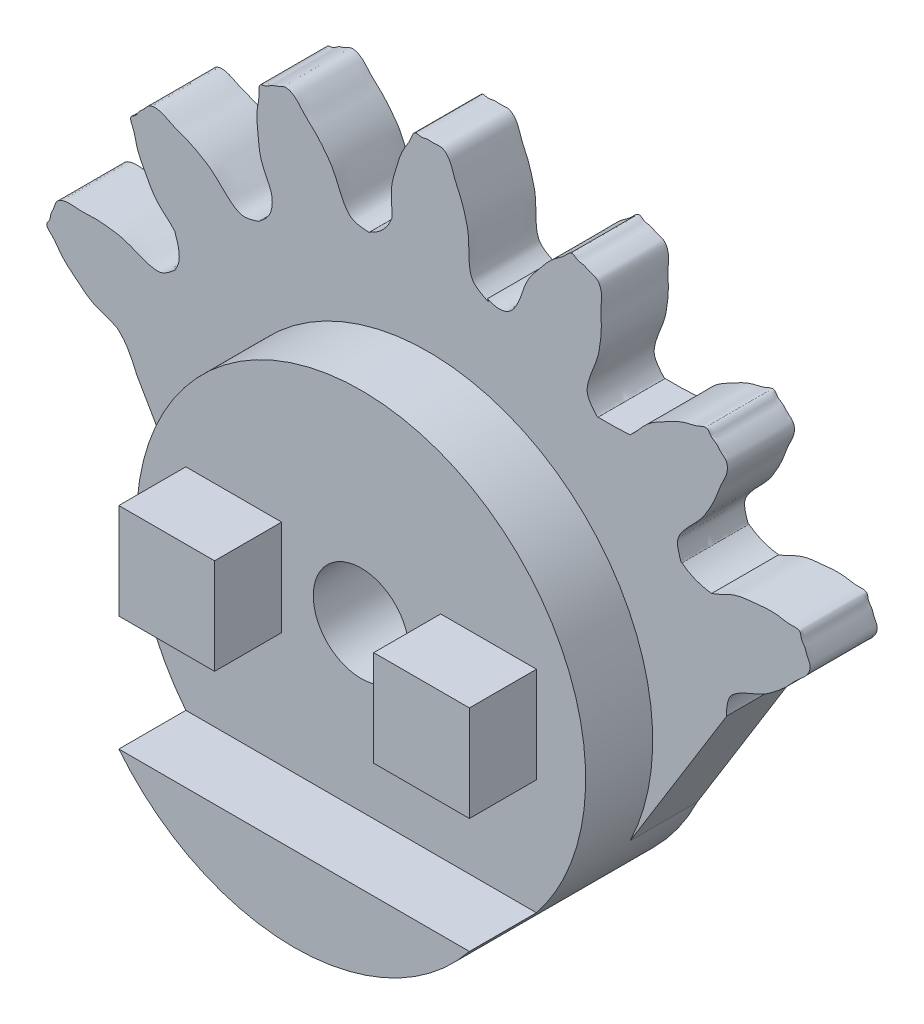
SolidWorks part; units mm, degrees
ref_plane "前视基准面" through (0, 0, 0) normal (0, 0, 1) x (1, 0, 0)
ref_plane "上视基准面" through (0, 0, 0) normal (0, 1, 0) x (1, 0, 0)
ref_plane "右视基准面" through (0, 0, 0) normal (1, 0, 0) x (0, 0, -1)
sketch "草图2" plane through (0, 0, 0) normal (0, 0, 1) x (1, 0, 0)
  line L0 (147.5, 353) -> (737.5, 353) construction
  line L1 (126.9453, 329.1282) -> (215.9062, 175.2157)
  line L2 (743.28, 329.1282) -> (642.0784, 165.4487)
  circle A0 centre (431.2319, 268.0573) radius 234.4883
  spline S0 degree 3 poles (106.1273, 361.6131) (98.4228, 365.6121) (82.8394, 368.5027) (67.6507, 380.9617) (55.592, 390.5905) (46.1074, 400.1016) (40.5186, 410.0482) (30.3288, 417.5544) (36.9425, 424.0464) (36.5344, 430.3043) (40.8328, 436.6029) (41.6046, 444.3035) (52.946, 450.5666) (65.8603, 447.7929) (81.8717, 449.2947) (96.1738, 448.2633) (112.2294, 446.0206) (128.5463, 439.2667) (147.8212, 431.8075) (158.9663, 436.9626) (170.5757, 447.057) (165.5512, 444.9951) knots 0 0 0 0 0.102585 0.179326 0.226624 0.285833 0.331169 0.372899 0.392635 0.423373 0.442181 0.480631 0.505916 0.582869 0.628674 0.694971 0.751247 0.816717 0.908849 0.960271 1 1 1 1
  spline S1 degree 3 poles (166.6767, 478.9038) (161.089, 485.5467) (147.7981, 494.1808) (138.5333, 511.5039) (131.0774, 525.0144) (125.9545, 537.4311) (124.5974, 548.7593) (118.0558, 559.5936) (126.6505, 563.0604) (128.6682, 568.9982) (135.0498, 573.1724) (138.7098, 579.9915) (151.5846, 581.4377) (162.4544, 573.933) (177.8217, 569.1933) (190.6404, 562.7671) (204.6156, 554.5509) (217.1058, 542.067) (232.0591, 527.7994) (244.3285, 528.297) (258.9172, 533.1803) (253.4861, 533.1981) knots 0 0 0 0 0.102585 0.179326 0.226624 0.285833 0.331169 0.372899 0.392635 0.423373 0.442181 0.480631 0.505916 0.582869 0.628674 0.694971 0.751247 0.816717 0.908849 0.960271 1 1 1 1
  spline S2 degree 3 poles (267.5022, 564.0949) (264.882, 572.3706) (255.9069, 585.4337) (253.9766, 604.9835) (252.2585, 620.3189) (252.2773, 633.7509) (255.3586, 644.7361) (253.4611, 657.2491) (262.7282, 657.163) (266.8646, 661.8765) (274.3578, 663.2909) (280.3488, 668.1903) (292.797, 664.5994) (299.9675, 653.5063) (312.3512, 643.2465) (321.735, 632.4041) (331.5021, 619.4652) (338.2642, 603.1517) (346.6192, 584.2478) (358.1451, 580.0123) (373.492, 578.941) (368.4812, 581.0359) knots 0 0 0 0 0.102585 0.179326 0.226624 0.285833 0.331169 0.372899 0.392635 0.423373 0.442181 0.480631 0.505916 0.582869 0.628674 0.694971 0.751247 0.816717 0.908849 0.960271 1 1 1 1
  spline S3 degree 3 poles (393.2541, 604.2171) (394.0003, 612.8654) (390.7074, 628.3688) (396.4055, 647.1692) (400.6867, 661.9947) (405.8443, 674.3971) (412.8949, 683.3669) (415.9303, 695.6536) (424.4591, 692.0277) (430.0845, 694.7995) (437.5485, 693.2387) (444.9583, 695.4725) (455.0848, 687.3912) (457.4644, 674.3985) (464.9791, 660.1807) (469.4994, 646.5725) (473.5716, 630.8808) (473.576, 613.2214) (474.0608, 592.5592) (483.0885, 584.2352) (496.8573, 577.3725) (493.0295, 581.2255) knots 0 0 0 0 0.102585 0.179326 0.226624 0.285833 0.331169 0.372899 0.392635 0.423373 0.442181 0.480631 0.505916 0.582869 0.628674 0.694971 0.751247 0.816717 0.908849 0.960271 1 1 1 1
  spline S4 degree 3 poles (524.7878, 593.1619) (528.7868, 600.8664) (531.6774, 616.4498) (544.1363, 631.6385) (553.7652, 643.6972) (563.2763, 653.1818) (573.2228, 658.7706) (580.7291, 668.9604) (587.221, 662.3467) (593.479, 662.7548) (599.7775, 658.4564) (607.4782, 657.6846) (613.7413, 646.3432) (610.9676, 633.4289) (612.4694, 617.4176) (611.438, 603.1154) (609.1953, 587.0599) (602.4414, 570.743) (594.9822, 551.468) (600.1372, 540.323) (610.2317, 528.7136) (608.1697, 533.7381) knots 0 0 0 0 0.102585 0.179326 0.226624 0.285833 0.331169 0.372899 0.392635 0.423373 0.442181 0.480631 0.505916 0.582869 0.628674 0.694971 0.751247 0.816717 0.908849 0.960271 1 1 1 1
  spline S5 degree 3 poles (642.0784, 532.6125) (648.7214, 538.2002) (657.3555, 551.4912) (674.6785, 560.7559) (688.189, 568.2119) (700.6058, 573.3347) (711.934, 574.6918) (722.7683, 581.2334) (726.2351, 572.6388) (732.1728, 570.621) (736.347, 564.2395) (743.1662, 560.5795) (744.6124, 547.7046) (737.1077, 536.8348) (732.3679, 521.4675) (725.9418, 508.6488) (717.7256, 494.6736) (705.2416, 482.1834) (690.974, 467.2302) (691.4716, 454.9607) (696.355, 440.3721) (696.3728, 445.8031) knots 0 0 0 0 0.102585 0.179326 0.226624 0.285833 0.331169 0.372899 0.392635 0.423373 0.442181 0.480631 0.505916 0.582869 0.628674 0.694971 0.751247 0.816717 0.908849 0.960271 1 1 1 1
  spline S6 degree 3 poles (727.2696, 431.787) (735.5452, 434.4072) (748.6083, 443.3823) (768.1582, 445.3126) (783.4935, 447.0307) (796.9256, 447.012) (807.9107, 443.9306) (820.4237, 445.8282) (820.3376, 436.5611) (825.0512, 432.4246) (826.4656, 424.9314) (831.365, 418.9405) (827.7741, 406.4922) (816.681, 399.3217) (806.4212, 386.9381) (795.5787, 377.5543) (782.6399, 367.7871) (766.3264, 361.0251) (747.4225, 352.6701) (743.1869, 341.1441) (742.1157, 325.7972) (744.2105, 330.8081) knots 0 0 0 0 0.102585 0.179326 0.226624 0.285833 0.331169 0.372899 0.392635 0.423373 0.442181 0.480631 0.505916 0.582869 0.628674 0.694971 0.751247 0.816717 0.908849 0.960271 1 1 1 1
  spline S7 degree 3 poles (166.6767, 478.9038) (170.3869, 468.5554) (174.4845, 455.7866) (167.397, 445.5249) knots 0 0 0 0 1 1 1 1
  spline S8 degree 2 poles (267.5022, 564.0949) (271.7915, 543.7429) (255.3941, 532.9813) knots 0 0 0 1 1 1
  spline S9 degree 2 poles (393.2541, 604.2171) (387.1781, 587.276) (370.161, 580.1053) knots 0 0 0 1 1 1
  spline S10 degree 2 poles (524.7878, 593.1619) (515.3006, 571.5328) (493.0295, 581.2255) knots 0 0 0 1 1 1
  spline S11 degree 2 poles (608.6996, 531.8923) (625.4024, 531.5836) (642.0784, 532.6125) knots 0 0 0 1 1 1
  spline S12 degree 2 poles (696.1559, 443.8951) (709.8525, 433.561) (727.2696, 431.787) knots 0 0 0 1 1 1
  spline S13 degree 3 poles (106.1273, 361.6131) (116.5021, 353.2443) (121.8907, 340.9954) (126.9453, 329.1282) knots 0 0 0 0 1 1 1 1
  point P159 (431.2319, 268.0573)
extrude "凸台-拉伸1" add sketch "草图2" against normal blind 70 contours S0 S13 L1 A0 L2 S6 S12 S5 S11 S4 S10 S3 S9 S2 S8 S1 S7 | L0 A0 | A0 L0 region at (431.2319, 414.8303, 0) region at (187.2165, 263.615, 0) region at (431.2319, 212.5148, 0)
extrude "凸台-拉伸2" add sketch "草图2<3>" along normal blind 70 contours L0 A0 | A0 L0 region at (431.2319, 414.8303, 0) region at (431.2319, 212.5148, 0)
sketch "草图2<3>" plane through (0, 0, 0) normal (0, 0, 1) x (1, 0, 0) same geometry as "草图2"
sketch "草图3" plane through (0, 0, 70) normal (0, 0, 1) x (1, 0, 0)
  line L0 (431.2319, 33.569) -> (431.2319, 694.1804) construction
  line L1 (614.3012, 241.7704) -> (514.3012, 241.7704)
  line L2 (248.1627, 241.7704) -> (348.1627, 241.7704)
  line L3 (248.1627, 241.7704) -> (248.1627, 341.7704)
  line L4 (248.1627, 341.7704) -> (348.1627, 341.7704)
  line L5 (348.1627, 241.7704) -> (348.1627, 341.7704)
  line L6 (614.3012, 241.7704) -> (614.3012, 341.7704)
  line L7 (614.3012, 341.7704) -> (514.3012, 341.7704)
  line L8 (514.3012, 241.7704) -> (514.3012, 341.7704)
  line L9 (248.1627, 121.5295) -> (614.3012, 121.5295)
  circle A0 centre (431.2319, 268.0573) radius 234.4883 construction
  circle A1 centre (431.2319, 291.7704) radius 50
  arc A2 (248.1627, 121.5295) -> (614.3012, 121.5295) centre (431.2319, 268.0573) ccw
  spline S0 degree 3 poles (393.2541, 604.2171) (394.0003, 612.8654) (390.7074, 628.3688) (396.4055, 647.1692) (400.6867, 661.9947) (405.8443, 674.3971) (412.8949, 683.3669) (415.9303, 695.6536) (424.4591, 692.0277) (430.0845, 694.7995) (437.5485, 693.2387) (444.9583, 695.4725) (455.0848, 687.3912) (457.4644, 674.3985) (464.9791, 660.1807) (469.4994, 646.5725) (473.5716, 630.8808) (473.576, 613.2214) (474.0608, 592.5592) (483.0885, 584.2352) (496.8573, 577.3725) (493.0295, 581.2255) knots 0 0 0 0 0.102585 0.179326 0.226624 0.285833 0.331169 0.372899 0.392635 0.423373 0.442181 0.480631 0.505916 0.582869 0.628674 0.694971 0.751247 0.816717 0.908849 0.960271 1 1 1 1 construction
  circle M10 centre (431.2319, 268.0573) radius 234.4883
  dimension "D3" = 100
  dimension "D1" = 100
  dimension "D2" = 100
extrude "凸台-拉伸3" add sketch "草图3" along normal blind 70 contours L2 L5 L4 L3 | L8 L1 L6 L7 region at (564.3012, 291.7704, 70) region at (298.1627, 291.7704, 70)
extrude "切除-拉伸1" cut sketch "草图3<3>" against normal through all contours L0 A1 | A1 L0 region at (410.0113, 291.7704, 70) region at (452.4526, 291.7704, 70)
sketch "草图3<3>" plane through (0, 0, 70) normal (0, 0, 1) x (1, 0, 0) same geometry as "草图3"
extrude "凸台-拉伸4" add sketch "草图3<5>" along normal through all contours L0 A2 L9 | L0 L9 M10 region at (360.4653, 85.7102, 70) region at (501.9986, 85.7102, 70)
sketch "草图3<5>" plane through (0, 0, 70) normal (0, 0, 1) x (1, 0, 0) same geometry as "草图3"
